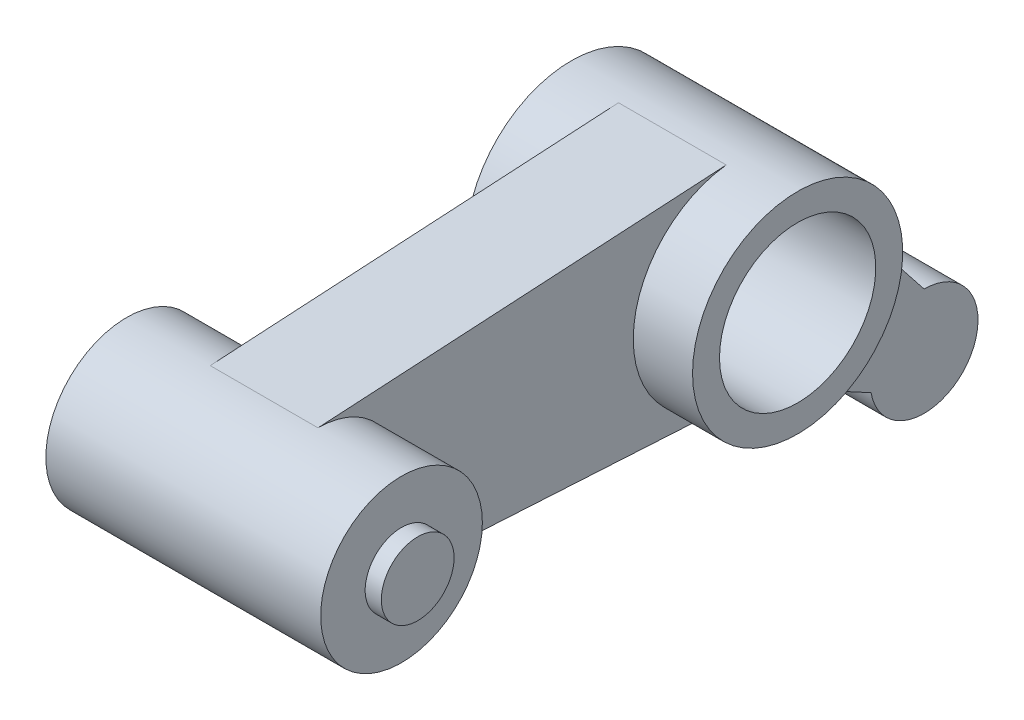
SolidWorks part; units mm, degrees
ref_plane "正面" through (0, 0, 0) normal (0, 0, 1) x (1, 0, 0)
ref_plane "平面" through (0, 0, 0) normal (0, 1, 0) x (1, 0, 0)
ref_plane "右側面" through (0, 0, 0) normal (1, 0, 0) x (0, 0, -1)
sketch "ｽｹｯﾁ1" plane through (0, 0, 0) normal (1, 0, 0) x (0, 0, -1)
  line L0 (0, 0) -> (-78, 0)
  line L1 (0, 0) -> (34.472, -28.9254)
  line L2 (-78, 15) -> (0, 19.5)
  line L3 (0, -19.5) -> (-78, -15)
  line L4 (19.5, 0) -> (34.472, -18.9254)
  line L5 (3.3861, -19.2038) -> (24.6239, -30.6619)
  circle A0 centre (0, 0) radius 19.5
  circle A1 centre (-78, 0) radius 15
  circle A2 centre (34.472, -28.9254) radius 10
  dimension "D3" = 39
  dimension "D4" = 30
  dimension "D5" = 20
  dimension "D6" = 78
  dimension "D1" = 45
  dimension "D2" = 140
extrude "ﾎﾞｽ - 押し出し1" add sketch "ｽｹｯﾁ1" along normal blind 10 and the other way blind 10 contours A1 | A1 L0 A0 L2 | A1 L3 A0 L0 | A0 L2 L0 L1 | L0 A0 L3 L1 | A2 L1 A0 L5 | A2 L4 A0 L1 | A2 region at (0, -9.3949, 3.4201) region at (0, 5.9783, -2.1765) region at (0, -9.2797, 40.2933) region at (0, 9.2797, 40.2933) region at (0, -12.8976, -23.859) region at (0, -21.2569, -16.8447) region at (0, -10.3066, 67.6934) region at (0, -20.1187, -30.3654)
extrude "ﾎﾞｽ - 押し出し2" add sketch "ｽｹｯﾁ1<3>" along normal blind 25.5 and the other way blind 25.5 contours A1 region at (0, -10.3066, 67.6934)
sketch "ｽｹｯﾁ1<3>" plane through (0, 0, 0) normal (1, 0, 0) x (0, 0, -1) same geometry as "ｽｹｯﾁ1"
sketch "ｽｹｯﾁ3" plane through (-25.5, 0, 0) normal (-1, 0, 0) x (0, 0, 1)
  line L0 (0, 0) -> (78, 0) construction
  circle A0 centre (78, 0) radius 8
  dimension "D1" = 16
extrude "ﾎﾞｽ - 押し出し3" add sketch "ｽｹｯﾁ3" along normal blind 3
sketch "ｽｹｯﾁ4" plane through (25.5, 0, 0) normal (1, 0, 0) x (0, 0, -1)
  line L0 (0, 0) -> (-78, 0) construction
  circle A1 centre (-78, 0) radius 6.75
  dimension "D1" = 13.5
extrude "ﾎﾞｽ - 押し出し4" add sketch "ｽｹｯﾁ4" along normal blind 3
sketch "ｽｹｯﾁ5" plane through (-10, 0, 0) normal (-1, 0, 0) x (0, 0, 1)
  circle A0 centre (0, 0) radius 14.5
  circle A1 centre (0, 0) radius 19.5
  dimension "D1" = 29
  dimension "D2" = 39
extrude "ﾎﾞｽ - 押し出し5" add sketch "ｽｹｯﾁ5" along normal blind 11 and the other way blind 31
extrude "ｶｯﾄ - 押し出し1" cut sketch "ｽｹｯﾁ5<2>" against normal blind 5 contours A0 region at (-10, 0, 0)
sketch "ｽｹｯﾁ5<2>" plane through (-10, 0, 0) normal (-1, 0, 0) x (0, 0, 1) same geometry as "ｽｹｯﾁ5"
sketch "ｽｹｯﾁ6" plane through (10, 0, 0) normal (1, 0, 0) x (0, 0, -1)
  circle A0 centre (0, 0) radius 14.5
  dimension "D1" = 29
extrude "ｶｯﾄ - 押し出し2" cut sketch "ｽｹｯﾁ6" against normal blind 5
sketch "ｽｹｯﾁ7" plane through (-5, 0, 0) normal (-1, 0, 0) x (0, 0, 1)
  circle A0 centre (0, 0) radius 6.75
  dimension "D1" = 13.5
extrude "ｶｯﾄ - 押し出し3" cut sketch "ｽｹｯﾁ7" against normal blind 15
sketch "ｽｹｯﾁ8" plane through (5, 0, 0) normal (1, 0, 0) x (0, 0, -1)
  circle A1 centre (0, 0) radius 8
  circle A2 centre (0, 0) radius 14.5
  dimension "D1" = 16
  dimension "D2" = 29
extrude "ｶｯﾄ - 押し出し4" cut sketch "ｽｹｯﾁ8" against normal blind 8
sketch "ｽｹｯﾁ9" plane through (5, 0, 0) normal (1, 0, 0) x (0, 0, -1)
  circle A0 centre (0, 0) radius 8.1486
  dimension "D1" = 16.2972
extrude "ｶｯﾄ - 押し出し5" cut sketch "ｽｹｯﾁ9" against normal blind 4
